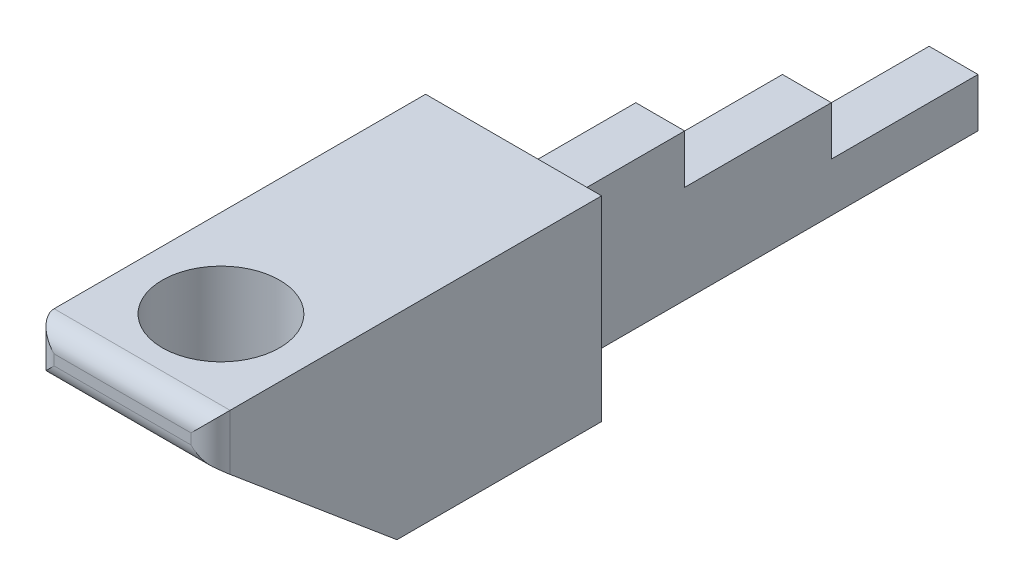
SolidWorks part; units mm, degrees
ref_plane "Спереди" through (0, 0, 0) normal (0, 0, 1) x (1, 0, 0)
ref_plane "Сверху" through (0, 0, 0) normal (0, 1, 0) x (1, 0, 0)
ref_plane "Справа" through (0, 0, 0) normal (1, 0, 0) x (0, 0, -1)
sketch "Эскиз1" plane through (0, 0, 0) normal (1, 0, 0) x (0, 0, -1)
  line L0 (0, 0) -> (-19.0681, 16)
  line L1 (-19.0681, 16) -> (-19.0681, 20)
  line L2 (-19.0681, 20) -> (20.9319, 20)
  line L3 (20.9319, 20) -> (20.9319, 0)
  line L4 (20.9319, 0) -> (0, 0)
  line L5 (20.9319, 15) -> (35.9319, 15)
  line L6 (35.9319, 15) -> (35.9319, 10)
  line L7 (35.9319, 10) -> (50.9319, 10)
  line L8 (50.9319, 10) -> (50.9319, 5)
  line L9 (50.9319, 5) -> (65.9319, 5)
  line L10 (65.9319, 5) -> (65.9319, 0)
  line L11 (65.9319, 0) -> (20.9319, 0)
  point P9 (-31.7409, 18.3256)
  point P14 (-21.7331, 12.5476)
  dimension "D1" = 140
  dimension "D2" = 20
  dimension "D3" = 15
  dimension "D4" = 5
  dimension "D5" = 4
  dimension "D6" = 40
  dimension "D7" = 5
  dimension "D8" = 15
  dimension "D9" = 15
  dimension "D10" = 15
extrude "Бобышка-Вытянуть1" add sketch "Эскиз1" along normal mid plane 18 contours L4 L3 L2 L1 L0 region at (0, 11.0995, -4.1465)
extrude "Бобышка-Вытянуть2" add sketch "Эскиз1<3>" along normal mid plane 5 contours L11 L10 L9 L8 L7 L6 L5 L3 region at (0, 5.8333, -38.4319)
sketch "Эскиз1<3>" plane through (0, 0, 0) normal (1, 0, 0) x (0, 0, -1) same geometry as "Эскиз1"
sketch "Эскиз2" plane through (0, 20, 0) normal (0, 1, 0) x (1, 0, 0)
  line L0 (-9, -19.0681) -> (-9, 20.9319) construction
  circle A0 centre (0, -9) radius 6
  dimension "D1" = 12
  dimension "D2" = 9
  dimension "D3" = 9
extrude "Вырез-Вытянуть1" cut sketch "Эскиз2" against normal blind 35
ref_plane "Плоскость4" through (9, 16, 19.0681) normal (0, 1, 0) x (1, 0, 0)
fillet "Скругление2" radius 2 4 edges at (0, 20, 19.0681) (9, 18, 19.0681) (0, 16, 19.0681) (-9, 18, 19.0681)
